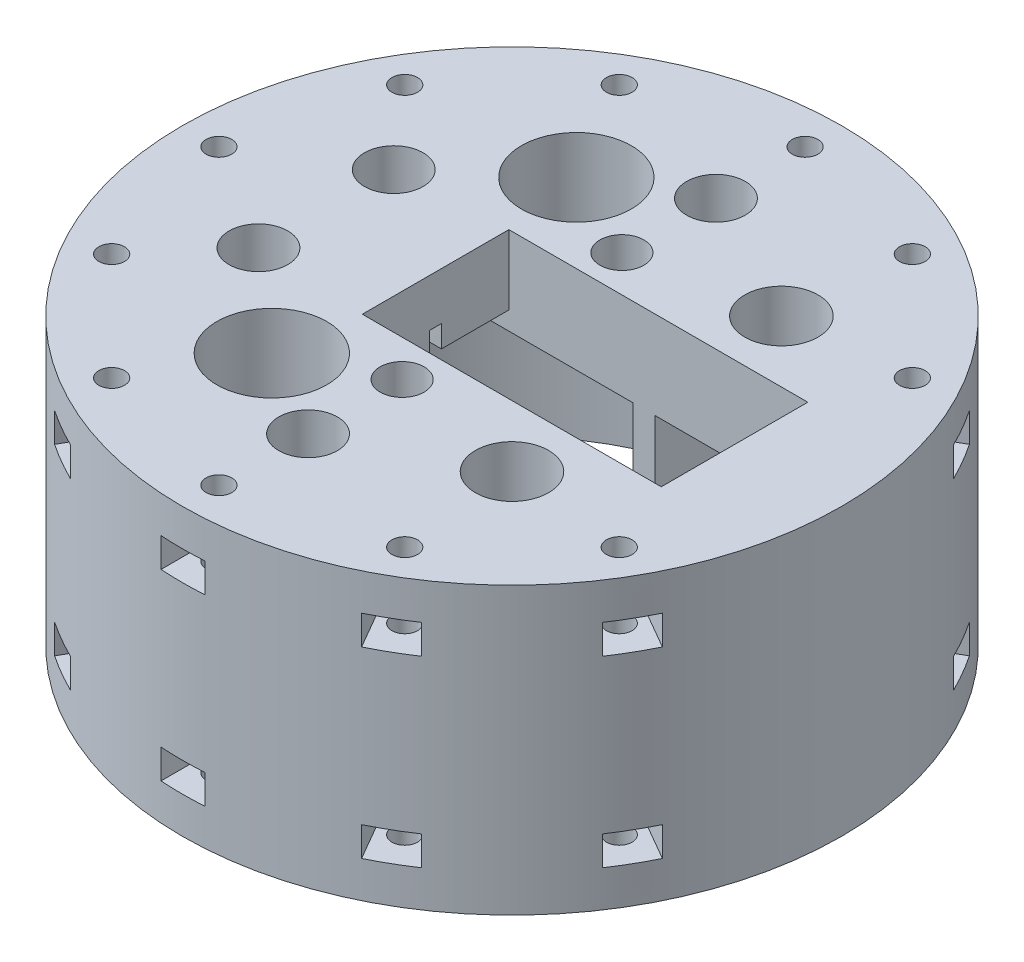
SolidWorks part; units mm, degrees
ref_plane "Front Plane" through (0, 0, 0) normal (0, 0, 1) x (1, 0, 0)
ref_plane "Top Plane" through (0, 0, 0) normal (0, 1, 0) x (1, 0, 0)
ref_plane "Right Plane" through (0, 0, 0) normal (1, 0, 0) x (0, 0, -1)
sketch "Sketch1" plane through (0, 0, 0) normal (0, 1, 0) x (1, 0, 0)
  line L0 (-43.0464, 0) -> (41.9462, 0) construction
  line L1 (0, 43.1152) -> (0, -41.8775) construction
  circle A1 centre (0, 0) radius 45
  dimension "D2" = 90
extrude "Boss-Extrude1" add sketch "Sketch1" along normal blind 39
sketch "Sketch2" plane through (0, 0, 0) normal (0, -1, 0) x (1, 0, 0)
  circle A0 centre (0, 0) radius 35
  dimension "D1" = 70
extrude "Cut-Extrude1" cut sketch "Sketch2" against normal blind 27
sketch "Sketch3" plane through (0, 27, 0) normal (0, -1, 0) x (1, 0, 0)
  line L0 (35, 0) -> (-35, 0) construction
  line L1 (0, -35) -> (0, 35) construction
  line L3 (37.5324, -10) -> (-17.4676, -10)
  line L4 (37.5324, -10) -> (37.5324, 10)
  line L5 (37.5324, 10) -> (-17.4676, 10)
  line L6 (-17.4676, -10) -> (-17.4676, 10)
  circle A0 centre (0, 0) radius 35 construction
  circle A1 centre (0, 0) radius 35 construction
  dimension "D1" = 20
  dimension "D2" = 55
  dimension "D3" = 10
  dimension "D4" = 37.5324
extrude "Cut-Extrude2" cut sketch "Sketch3" against normal blind 2.5 and the other way up to next
sketch "Sketch4" plane through (0, 29.5, 0) normal (0, -1, 0) x (1, 0, 0)
  line L0 (37.5324, 0) -> (-17.4676, 0) construction
  line L1 (37.5324, 10) -> (37.5324, -10) construction
  line L2 (-17.4676, 10) -> (-17.4676, -10) construction
  line L3 (0, -10) -> (0, 10) construction
  line L4 (-17.4676, -10) -> (33.541, -10) construction
  line L5 (33.541, 10) -> (-17.4676, 10) construction
  line L7 (30.3722, -10) -> (-10.4278, -10)
  line L8 (30.3722, -10) -> (30.3722, 10)
  line L9 (30.3722, 10) -> (-10.4278, 10)
  line L10 (-10.4278, -10) -> (-10.4278, 10)
  dimension "D1" = 20
  dimension "D2" = 40.8
  dimension "D3" = 30.3722
  dimension "D4" = 10
extrude "Cut-Extrude3" cut sketch "Sketch4" against normal blind 10.5
sketch "Sketch8" plane through (0, 27, 0) normal (0, -1, 0) x (1, 0, 0)
  line L0 (-17.4676, 0) -> (-35, 0) construction
  line L1 (-17.4676, 10) -> (-17.4676, -10) construction
  line L2 (8.0367, 10) -> (8.0367, 34.0648) construction
  line L3 (33.541, 10) -> (-17.4676, 10) construction
  line L4 (8.0367, -10) -> (8.0367, -29.3194) construction
  line L5 (-17.4676, -10) -> (33.541, -10) construction
  line L6 (6.5367, 10) -> (6.5367, 34.3842)
  line L7 (9.5367, 10) -> (9.5367, 33.6757)
  line L8 (9.5367, 10) -> (6.5367, 10)
  line L9 (9.5367, -10) -> (6.5367, -10)
  line L10 (6.5367, -10) -> (6.5367, -34.3842)
  line L11 (9.5367, -10) -> (9.5367, -33.6757)
  line L12 (-17.4676, 1.5) -> (-34.9678, 1.5)
  line L13 (-17.4676, -1.5) -> (-34.9678, -1.5)
  line L14 (-17.4676, 1.5) -> (-17.4676, -1.5)
  arc A0 (33.541, 10) -> (33.541, -10) centre (0, 0) ccw construction
  arc A1 (9.5367, 33.6757) -> (6.5367, 34.3842) centre (7.9531, 33.6757) ccw
  arc A2 (9.5367, -33.6757) -> (6.5367, -34.3842) centre (7.9531, -33.6757) cw
  arc A3 (-34.9678, 1.5) -> (-34.9678, -1.5) centre (-34.9678, 0) ccw
  dimension "D3" = 1.5
  dimension "D1" = 1.5
  dimension "D2" = 1.5
  dimension "D4" = 1.5
extrude "Boss-Extrude2" add sketch "Sketch8" along normal through all
sketch "Sketch13" plane through (0, 27, 0) normal (0, -1, 0) x (1, 0, 0)
  line L0 (0, 0) -> (0, 35) construction
  line L1 (0, 0) -> (-17.5, 30.3109) construction
  line L2 (0, 0) -> (-41.2446, 0) construction
  line L3 (-32.8892, 11.9707) -> (0, 0) construction
  line L5 (0, 0) -> (24.7487, 24.7487) construction
  arc A0 (6.5367, 34.3842) -> (-34.9678, 1.5) centre (0, 0) ccw construction
  circle A1 centre (-12, 20.7846) radius 7.5
  circle A2 centre (-25.3717, 9.2345) radius 4
  arc A3 (33.541, 10) -> (9.5367, 33.6757) centre (0, 0) ccw construction
  circle A4 centre (18.3848, 18.3848) radius 5
  circle A5 centre (18.3848, -18.3848) radius 5
  circle A6 centre (-12, -20.7846) radius 7.5
  circle A7 centre (-25.3717, -9.2345) radius 4
  circle A8 centre (0, -15) radius 3
  circle A9 centre (0, -27.8351) radius 4
  circle A10 centre (0, 27.8351) radius 4
  circle A11 centre (0, 15) radius 3
  dimension "D3" = 15
  dimension "D6" = 8
  dimension "D8" = 10
  dimension "D10" = 8
  dimension "D11" = 6
  dimension "D1" = 30
  dimension "D2" = 20
  dimension "D4" = 27
  dimension "D5" = 24
  dimension "D7" = 45
  dimension "D9" = 26
  dimension "D12" = 15
extrude "Cut-Extrude7" cut sketch "Sketch13" against normal through all
sketch "Sketch15" plane through (0, 0, -1.5) normal (0, 0, -1) x (-1, 0, 0)
  line L0 (34.9678, 0) -> (17.4676, 27)
  line L1 (17.4676, 27) -> (17.4676, 0)
  line L3 (17.4676, 0) -> (34.9678, 0)
extrude "Cut-Extrude8" cut sketch "Sketch15" against normal blind 3
sketch "Sketch16" plane through (0, 29.5, 0) normal (0, -1, 0) x (1, 0, 0)
  line L0 (-17.4676, 0) -> (37.5324, 0) construction
  line L1 (-17.4676, 10) -> (-17.4676, -10) construction
  line L2 (37.5324, -10) -> (37.5324, 10) construction
  line L3 (30.3722, -0.8) -> (37.5324, -0.8)
  line L4 (-10.4278, -0.8) -> (-17.4676, -0.8)
  line L5 (-10.4278, 10) -> (-10.4278, -10) construction
  line L6 (-10.4278, 0.8) -> (-17.4676, 0.8)
  line L7 (-17.4676, 0.8) -> (-17.4676, -0.8)
  line L8 (-10.4278, 0.8) -> (-10.4278, -0.8)
  line L9 (30.3722, -10) -> (30.3722, 10) construction
  line L10 (30.3722, 0.8) -> (37.5324, 0.8)
  line L11 (37.5324, 0.8) -> (37.5324, -0.8)
  line L12 (30.3722, 0.8) -> (30.3722, -0.8)
  dimension "D1" = 0.8
extrude "Cut-Extrude10" cut sketch "Sketch16" against normal blind 3
sketch "Sketch27" plane through (0, 0, 0) normal (0, -1, 0) x (1, 0, 0)
  line L0 (0, 0) -> (0, -53.17) construction
  line L1 (0, 0) -> (47.7582, -27.5732) construction
  line L3 (31.641, -18.2679) -> (31.641, -21.7321) construction
  line L4 (31.641, -21.7321) -> (34.641, -23.4641) construction
  line L5 (34.641, -23.4641) -> (37.641, -21.7321) construction
  line L6 (37.641, -21.7321) -> (37.641, -18.2679) construction
  line L7 (37.641, -18.2679) -> (34.641, -16.5359) construction
  line L8 (34.641, -16.5359) -> (31.641, -18.2679) construction
  circle A0 centre (0, 0) radius 40 construction
  circle A1 centre (34.641, -20) radius 1.75
  circle A2 centre (0, 0) radius 35 construction
  circle A3 centre (34.641, -20) radius 3 construction
  circle A4 centre (20, -34.641) radius 1.75
  circle A5 centre (0, -40) radius 1.75
  circle A6 centre (-20, -34.641) radius 1.75
  circle A7 centre (-34.641, -20) radius 1.75
  circle A8 centre (-40, 0) radius 1.75
  circle A9 centre (-34.641, 20) radius 1.75
  circle A10 centre (-20, 34.641) radius 1.75
  circle A11 centre (0, 40) radius 1.75
  circle A12 centre (20, 34.641) radius 1.75
  circle A13 centre (34.641, 20) radius 1.75
  circle A15 centre (40, 0) radius 1.75 [skipped]
  point P28 (0, 0)
  point P41 (0, 0)
  dimension "D1" = 80
  dimension "D3" = 3.5
  dimension "D4" = 70
  dimension "D5" = 6
  dimension "D6" = 12
  dimension "D2" = 60
extrude "Cut-Extrude15" cut sketch "Sketch27" against normal through all
ref_plane "Plane1" through (0, 34, 0) normal (0, 1, 0) x (1, 0, 0)
sketch "Sketch28" plane through (0, 34, 0) normal (0, 1, 0) x (1, 0, 0)
  line L0 (0, 0) -> (-54.493, 0) construction
  line L1 (-31.641, 18.2679) -> (-31.641, 21.7321)
  line L2 (-36.5359, 0) -> (-38.2679, 3)
  line L3 (-38.2679, 3) -> (-44.8999, 3)
  line L4 (-31.641, 21.7321) -> (-37.3844, 25.048)
  line L5 (-40.3844, 19.8519) -> (-34.641, 16.5359)
  line L6 (-44.8999, -3) -> (-38.2679, -3)
  line L7 (-38.2679, -3) -> (-36.5359, 0)
  line L8 (-43.4641, 0) -> (-42.5981, -1.5) [skipped]
  line L9 (-41.7321, 3) -> (-42.5981, 1.5) [skipped]
  line L10 (-34.641, 16.5359) -> (-31.641, 18.2679)
  line L11 (-18.2679, 31.641) -> (-16.5359, 34.641)
  line L12 (-16.5359, 34.641) -> (-19.8519, 40.3844)
  line L13 (-25.048, 37.3844) -> (-21.7321, 31.641)
  line L14 (-21.7321, 31.641) -> (-18.2679, 31.641)
  line L15 (0, 36.5359) -> (3, 38.2679)
  line L16 (3, 38.2679) -> (3, 44.8999)
  line L17 (-3, 44.8999) -> (-3, 38.2679)
  line L18 (-3, 38.2679) -> (0, 36.5359)
  line L19 (18.2679, 31.641) -> (21.7321, 31.641)
  line L20 (21.7321, 31.641) -> (25.048, 37.3844)
  line L21 (19.8519, 40.3844) -> (16.5359, 34.641)
  line L22 (16.5359, 34.641) -> (18.2679, 31.641)
  line L23 (31.641, 18.2679) -> (34.641, 16.5359)
  line L24 (34.641, 16.5359) -> (40.3844, 19.8519)
  line L25 (37.3844, 25.048) -> (31.641, 21.7321)
  line L26 (31.641, 21.7321) -> (31.641, 18.2679)
  line L31 (31.641, -18.2679) -> (31.641, -21.7321)
  line L32 (31.641, -21.7321) -> (37.3844, -25.048)
  line L33 (40.3844, -19.8519) -> (34.641, -16.5359)
  line L34 (34.641, -16.5359) -> (31.641, -18.2679)
  line L35 (18.2679, -31.641) -> (16.5359, -34.641)
  line L36 (16.5359, -34.641) -> (19.8519, -40.3844)
  line L37 (25.048, -37.3844) -> (21.7321, -31.641)
  line L38 (21.7321, -31.641) -> (18.2679, -31.641)
  line L39 (0, -36.5359) -> (-3, -38.2679)
  line L40 (-3, -38.2679) -> (-3, -44.8999)
  line L41 (3, -44.8999) -> (3, -38.2679)
  line L42 (3, -38.2679) -> (0, -36.5359)
  line L43 (-18.2679, -31.641) -> (-21.7321, -31.641)
  line L44 (-21.7321, -31.641) -> (-25.048, -37.3844)
  line L45 (-19.8519, -40.3844) -> (-16.5359, -34.641)
  line L46 (-16.5359, -34.641) -> (-18.2679, -31.641)
  line L47 (-31.641, -18.2679) -> (-34.641, -16.5359)
  line L48 (-34.641, -16.5359) -> (-40.3844, -19.8519)
  line L49 (-37.3844, -25.048) -> (-31.641, -21.7321)
  line L50 (-31.641, -21.7321) -> (-31.641, -18.2679)
  line L51 (36.5359, 0) -> (38.2679, -3) [skipped]
  line L52 (38.2679, -3) -> (44.8999, -3) [skipped]
  line L53 (44.8999, 3) -> (38.2679, 3) [skipped]
  line L54 (38.2679, 3) -> (36.5359, 0) [skipped]
  arc A0 (-44.8999, 3) -> (-44.8999, -3) centre (0, 0) ccw
  circle A1 centre (-40, 0) radius 3 construction
  arc A2 (-37.3844, 25.048) -> (-40.3844, 19.8519) centre (0, 0) ccw
  circle A3 centre (-34.641, 20) radius 3 construction
  arc A4 (-19.8519, 40.3844) -> (-25.048, 37.3844) centre (0, 0) ccw
  circle A5 centre (-20, 34.641) radius 3 construction
  arc A6 (3, 44.8999) -> (-3, 44.8999) centre (0, 0) ccw
  circle A7 centre (0, 40) radius 3 construction
  arc A8 (25.048, 37.3844) -> (19.8519, 40.3844) centre (0, 0) ccw
  circle A9 centre (20, 34.641) radius 3 construction
  arc A10 (40.3844, 19.8519) -> (37.3844, 25.048) centre (0, 0) ccw
  circle A11 centre (34.641, 20) radius 3 construction
  arc A14 (37.3844, -25.048) -> (40.3844, -19.8519) centre (0, 0) ccw
  circle A15 centre (34.641, -20) radius 3 construction
  arc A16 (19.8519, -40.3844) -> (25.048, -37.3844) centre (0, 0) ccw
  circle A17 centre (20, -34.641) radius 3 construction
  arc A18 (-3, -44.8999) -> (3, -44.8999) centre (0, 0) ccw
  circle A19 centre (0, -40) radius 3 construction
  arc A20 (-25.048, -37.3844) -> (-19.8519, -40.3844) centre (0, 0) ccw
  circle A21 centre (-20, -34.641) radius 3 construction
  arc A22 (-40.3844, -19.8519) -> (-37.3844, -25.048) centre (0, 0) ccw
  circle A23 centre (-34.641, -20) radius 3 construction
  arc A24 (44.8999, -3) -> (44.8999, 3) centre (0, 0) ccw [skipped]
  circle A25 centre (40, 0) radius 3 construction
  point P94 (0, 0)
  dimension "D1" = 90
  dimension "D2" = 6
  dimension "D3" = 12
extrude "Cut-Extrude17" cut sketch "Sketch28" against normal blind 4
ref_plane "Plane2" through (0, 5, 0) normal (0, -1, 0) x (-1, 0, 0)
sketch "Sketch30" plane through (0, 5, 0) normal (0, -1, 0) x (-1, 0, 0)
  line L0 (0, 0) -> (56.1913, 0) construction
  line L1 (31.641, -18.2679) -> (31.641, -21.7321)
  line L2 (36.5359, 0) -> (38.2679, -3)
  line L3 (38.2679, -3) -> (44.8999, -3)
  line L4 (31.641, -21.7321) -> (37.3844, -25.048)
  line L5 (40.3844, -19.8519) -> (34.641, -16.5359)
  line L6 (44.8999, 3) -> (38.2679, 3)
  line L7 (38.2679, 3) -> (36.5359, 0)
  line L8 (43.4641, 0) -> (42.5981, 1.5) [skipped]
  line L9 (41.7321, -3) -> (42.5981, -1.5) [skipped]
  line L10 (34.641, -16.5359) -> (31.641, -18.2679)
  line L11 (18.2679, -31.641) -> (16.5359, -34.641)
  line L12 (16.5359, -34.641) -> (19.8519, -40.3844)
  line L13 (25.048, -37.3844) -> (21.7321, -31.641)
  line L14 (21.7321, -31.641) -> (18.2679, -31.641)
  line L15 (0, -36.5359) -> (-3, -38.2679)
  line L16 (-3, -38.2679) -> (-3, -44.8999)
  line L17 (3, -44.8999) -> (3, -38.2679)
  line L18 (3, -38.2679) -> (0, -36.5359)
  line L19 (-18.2679, -31.641) -> (-21.7321, -31.641)
  line L20 (-21.7321, -31.641) -> (-25.048, -37.3844)
  line L21 (-19.8519, -40.3844) -> (-16.5359, -34.641)
  line L22 (-16.5359, -34.641) -> (-18.2679, -31.641)
  line L23 (-31.641, -18.2679) -> (-34.641, -16.5359)
  line L24 (-34.641, -16.5359) -> (-40.3844, -19.8519)
  line L25 (-37.3844, -25.048) -> (-31.641, -21.7321)
  line L26 (-31.641, -21.7321) -> (-31.641, -18.2679)
  line L31 (-31.641, 18.2679) -> (-31.641, 21.7321)
  line L32 (-31.641, 21.7321) -> (-37.3844, 25.048)
  line L33 (-40.3844, 19.8519) -> (-34.641, 16.5359)
  line L34 (-34.641, 16.5359) -> (-31.641, 18.2679)
  line L35 (-18.2679, 31.641) -> (-16.5359, 34.641)
  line L36 (-16.5359, 34.641) -> (-19.8519, 40.3844)
  line L37 (-25.048, 37.3844) -> (-21.7321, 31.641)
  line L38 (-21.7321, 31.641) -> (-18.2679, 31.641)
  line L39 (0, 36.5359) -> (3, 38.2679)
  line L40 (3, 38.2679) -> (3, 44.8999)
  line L41 (-3, 44.8999) -> (-3, 38.2679)
  line L42 (-3, 38.2679) -> (0, 36.5359)
  line L43 (18.2679, 31.641) -> (21.7321, 31.641)
  line L44 (21.7321, 31.641) -> (25.048, 37.3844)
  line L45 (19.8519, 40.3844) -> (16.5359, 34.641)
  line L46 (16.5359, 34.641) -> (18.2679, 31.641)
  line L47 (31.641, 18.2679) -> (34.641, 16.5359)
  line L48 (34.641, 16.5359) -> (40.3844, 19.8519)
  line L49 (37.3844, 25.048) -> (31.641, 21.7321)
  line L50 (31.641, 21.7321) -> (31.641, 18.2679)
  line L51 (-36.5359, 0) -> (-38.2679, 3) [skipped]
  line L52 (-38.2679, 3) -> (-44.8999, 3) [skipped]
  line L53 (-44.8999, -3) -> (-38.2679, -3) [skipped]
  line L54 (-38.2679, -3) -> (-36.5359, 0) [skipped]
  arc A0 (44.8999, -3) -> (44.8999, 3) centre (0, 0) ccw
  circle A1 centre (40, 0) radius 3 construction
  arc A2 (37.3844, -25.048) -> (40.3844, -19.8519) centre (0, 0) ccw
  circle A3 centre (34.641, -20) radius 3 construction
  arc A4 (19.8519, -40.3844) -> (25.048, -37.3844) centre (0, 0) ccw
  circle A5 centre (20, -34.641) radius 3 construction
  arc A6 (-3, -44.8999) -> (3, -44.8999) centre (0, 0) ccw
  circle A7 centre (0, -40) radius 3 construction
  arc A8 (-25.048, -37.3844) -> (-19.8519, -40.3844) centre (0, 0) ccw
  circle A9 centre (-20, -34.641) radius 3 construction
  arc A10 (-40.3844, -19.8519) -> (-37.3844, -25.048) centre (0, 0) ccw
  circle A11 centre (-34.641, -20) radius 3 construction
  arc A14 (-37.3844, 25.048) -> (-40.3844, 19.8519) centre (0, 0) ccw
  circle A15 centre (-34.641, 20) radius 3 construction
  arc A16 (-19.8519, 40.3844) -> (-25.048, 37.3844) centre (0, 0) ccw
  circle A17 centre (-20, 34.641) radius 3 construction
  arc A18 (3, 44.8999) -> (-3, 44.8999) centre (0, 0) ccw
  circle A19 centre (0, 40) radius 3 construction
  arc A20 (25.048, 37.3844) -> (19.8519, 40.3844) centre (0, 0) ccw
  circle A21 centre (20, 34.641) radius 3 construction
  arc A22 (40.3844, 19.8519) -> (37.3844, 25.048) centre (0, 0) ccw
  circle A23 centre (34.641, 20) radius 3 construction
  arc A24 (-44.8999, 3) -> (-44.8999, -3) centre (0, 0) ccw [skipped]
  circle A25 centre (-40, 0) radius 3 construction
  point P94 (0, 0)
  dimension "D1" = 90
  dimension "D2" = 6
  dimension "D3" = 12
extrude "Cut-Extrude19" cut sketch "Sketch30" against normal blind 4
